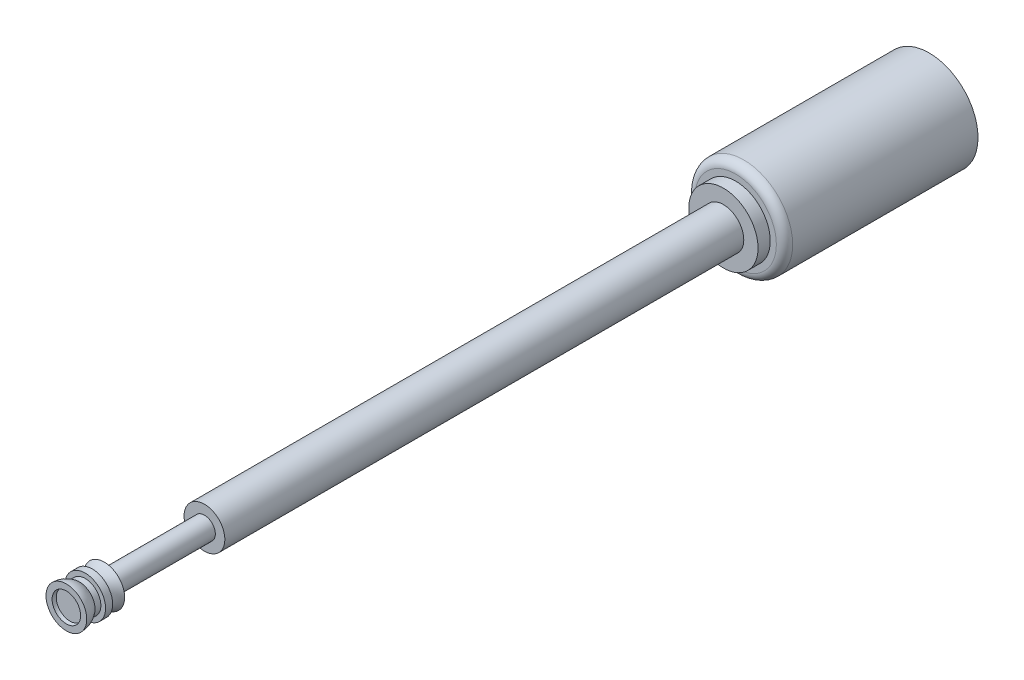
SolidWorks part; units mm, degrees
ref_plane "Front Plane" through (0, 0, 0) normal (0, 0, 1) x (1, 0, 0)
ref_plane "Top Plane" through (0, 0, 0) normal (0, 1, 0) x (1, 0, 0)
ref_plane "Right Plane" through (0, 0, 0) normal (1, 0, 0) x (0, 0, -1)
sketch "Sketch1" plane through (0, 0, 0) normal (0, 0, 1) x (1, 0, 0)
  circle A0 centre (0, 0) radius 0.5
  circle A1 centre (0, 0) radius 1.2
  dimension "D1" = 1
  dimension "D2" = 2.4
extrude "Boss-Extrude1" add sketch "Sketch1" along normal blind 15.5 contours A0
extrude "Boss-Extrude2" add sketch "Sketch1<3>" against normal blind 4.75 separate body
sketch "Sketch1<3>" plane through (0, 0, 0) normal (0, 0, 1) x (1, 0, 0) same geometry as "Sketch1"
fillet "Fillet1" radius 0.2 1 edges at (1.2, 0, 0)
sketch "Sketch2" plane through (0, 0, 0) normal (0, 0, 1) x (1, 0, 0)
  circle A0 centre (0, 0) radius 0.85
  dimension "D1" = 1.7
extrude "Boss-Extrude3" add sketch "Sketch2" along normal blind 0.3
sketch "Sketch3" plane through (0, 0, 0) normal (0, 1, 0) x (1, 0, 0)
  line L0 (0.5, -15.5) -> (0, -15.5)
  line L1 (-0.5, -15.5) -> (0.5, -15.5) construction
  line L2 (0, -15.5) -> (0, -16.08)
  line L3 (0.35, -16.43) -> (0.5, -16.43)
  line L4 (0.3853, -16.1114) -> (0.3853, -15.968)
  line L5 (0.3853, -15.968) -> (0.5, -15.968)
  line L6 (0.5, -15.968) -> (0.5, -15.7933)
  line L7 (0.5, -15.7933) -> (0.4161, -15.7933)
  arc A0 (0, -16.08) -> (0.35, -16.43) centre (0, -16.43) cw
  arc A1 (0.5, -16.43) -> (0.3853, -16.1114) centre (0, -16.43) ccw
  arc A2 (0.4161, -15.7933) -> (0.5, -15.5) centre (0.9705, -15.7933) cw
  point P9 (0.4161, -15.7933)
  point P17 (0, 0)
  point P18 (0, 0)
  dimension "D2" = 0.35
  dimension "D3" = 0.5
  dimension "D1" = 0.93
revolve "Revolve1" add sketch "Sketch3" angle 360 about L2
sketch "Sketch4" plane through (0, 0, 0) normal (0, 1, 0) x (1, 0, 0)
  line L0 (0, -15.5) -> (0, -16.4227) construction
  line L1 (0.5, -15.5) -> (-0.5, -15.5) construction
  line L3 (0, -16.34) -> (-0.4719, -16.34)
  line L4 (0, -16.34) -> (0, -16.3037)
  line L5 (0, -16.3037) -> (-0.4719, -16.3037)
  line L6 (-0.4719, -16.34) -> (-0.4719, -16.3037)
  dimension "D1" = 0.84
  dimension "D2" = 0.0363
revolve "Revolve2" add sketch "Sketch4" angle 360 about L0
sketch "Sketch5" plane through (0, 0, 0) normal (0, 1, 0) x (1, 0, 0)
  line L0 (0.5, -15.5) -> (-0.5, -15.5) construction
  line L1 (-0.267, -15.5) -> (-1.2439, -15.5)
  line L2 (-0.267, -15.5) -> (-0.267, -13.04)
  line L3 (-0.267, -13.04) -> (-1.2439, -13.04)
  line L4 (-1.2439, -15.5) -> (-1.2439, -13.04)
  line L5 (0, -15.5) -> (0, -16.4209) construction
  dimension "D1" = 0.267
  dimension "D2" = 2.46
revolve "Cut-Revolve1" cut sketch "Sketch5" angle 360 about L5
sketch "Sketch6" plane through (0, 0, -4.75) normal (0, 0, -1) x (-1, 0, 0)
  circle A0 centre (0, 0) radius 0.5 construction
  circle A1 centre (0, 0) radius 0.5
extrude "Boss-Extrude5" add sketch "Sketch6" against normal blind 0.3
sketch "Sketch7" plane through (0, 0, -4.75) normal (0, 0, -1) x (-1, 0, 0)
  point P0 (0, 0)
